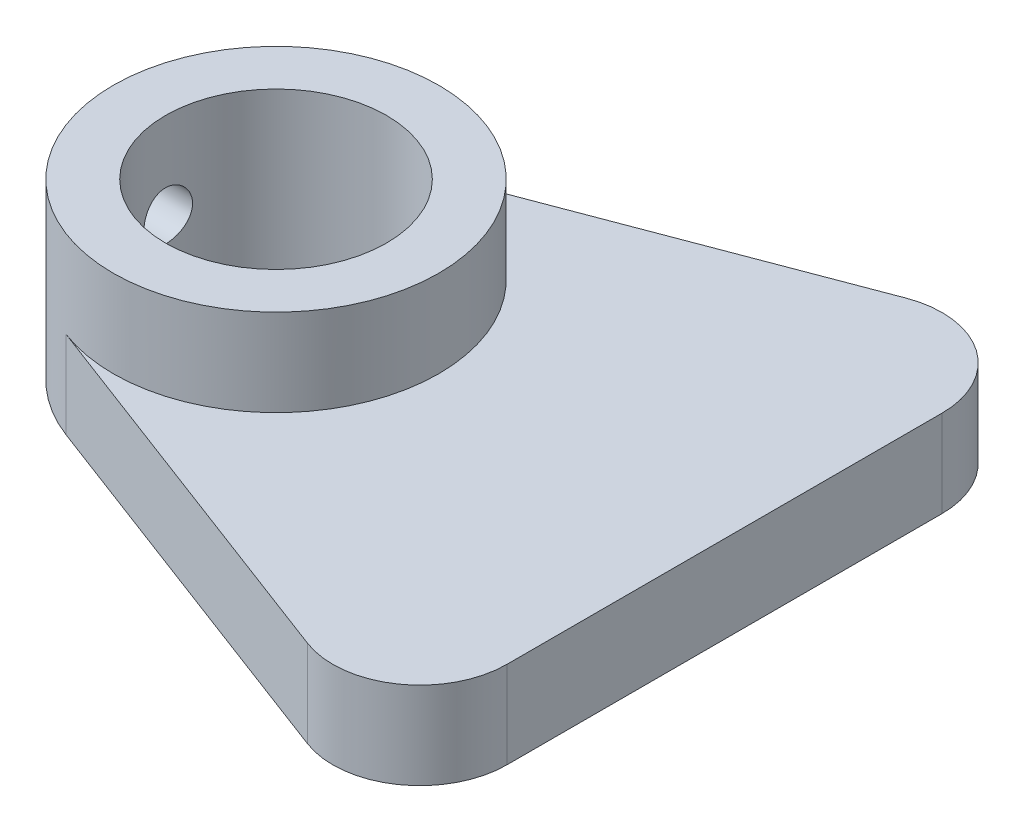
SolidWorks part; units mm, degrees
ref_plane "Front Plane" through (0, 0, 0) normal (0, 0, 1) x (1, 0, 0)
ref_plane "Top Plane" through (0, 0, 0) normal (0, 1, 0) x (1, 0, 0)
ref_plane "Right Plane" through (0, 0, 0) normal (1, 0, 0) x (0, 0, -1)
sketch "Sketch1" plane through (0, 0, 0) normal (0, 1, 0) x (1, 0, 0)
  line L0 (0, 0) -> (20.76, -12.5) construction
  line L1 (20.76, -12.5) -> (20.76, 12.5) construction
  line L2 (20.76, 12.5) -> (0, 0) construction
  line L3 (-3.3068, 8.7457) -> (18.9917, 17.1769)
  line L4 (25.76, 12.5) -> (25.76, -12.5)
  line L5 (0, 0) -> (25.76, 0) construction
  line L6 (-3.3068, -8.7457) -> (18.9917, -17.1769)
  circle A0 centre (0, 0) radius 6.35
  circle A1 centre (20.76, 12.5) radius 5
  circle A2 centre (20.76, -12.5) radius 5
  circle A3 centre (0, 0) radius 9.35
  dimension "D1" = 12.7
  dimension "D2" = 3
  dimension "D5" = 10
  dimension "D3" = 25.76
  dimension "D4" = 25
extrude "Boss-Extrude1" add sketch "Sketch1" along normal blind 5 contours A3 A0 | A3 L6 A2 L4 A1 L3 | A1 | A2 region at (14.6, 0, 0) region at (5.1649, 0, -7.4747) region at (20.76, 0, -12.5) region at (20.76, 0, 12.5)
extrude "Boss-Extrude2" add sketch "Sketch1<3>" along normal blind 10 contours A3 A0 region at (5.1649, 0, -7.4747)
sketch "Sketch1<3>" plane through (0, 0, 0) normal (0, 1, 0) x (1, 0, 0) same geometry as "Sketch1"
sketch "Sketch2" plane through (0, 0, 0) normal (1, 0, 0) x (0, 0, -1)
  line L0 (12.5, 5) -> (-12.5, 5) construction
  circle A0 centre (0, 5) radius 1.4
  dimension "D1" = 2.8
extrude "Cut-Extrude1" cut sketch "Sketch2" against normal through all
equation "\"m3 hole\"= 3.2"
equation "\"m4 hole\"= 4.2"
equation "\"m5 hole\"= 5.2"
equation "\"m6 hole\"= 6.2"
equation "\"m8 hole\"= 8.2"
equation "\"m3 tapped\"= 2.5"
equation "\"m4 tapped\"= 3.3"
equation "\"m5 tapped\"= 4.2"
equation "\"m6 tapped\"= 5"
equation "\"m8 tapped\"= 6.8"
